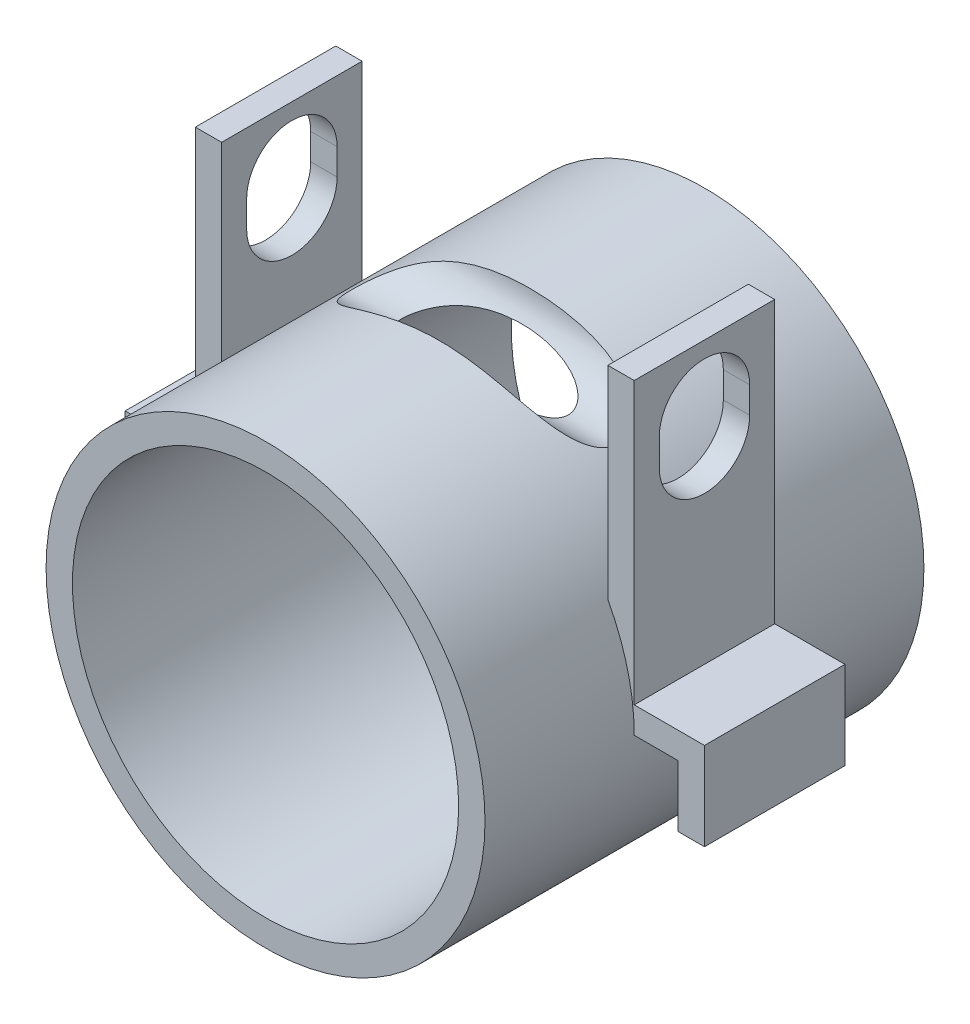
SolidWorks part; units mm, degrees
ref_plane "Front Plane" through (0, 0, 0) normal (0, 0, 1) x (1, 0, 0)
ref_plane "Top Plane" through (0, 0, 0) normal (0, 1, 0) x (1, 0, 0)
ref_plane "Right Plane" through (0, 0, 0) normal (1, 0, 0) x (0, 0, -1)
sketch "Sketch1" plane through (0, 0, 0) normal (0, 0, 1) x (1, 0, 0)
  circle A0 centre (0, 0) radius 22
  circle A1 centre (0, 0) radius 25
  dimension "D1" = 44
  dimension "D2" = 3
extrude "Boss-Extrude1" add sketch "Sketch1" along normal blind 50
ref_plane "Plane1" through (0, 0, 25) normal (0, 0, 1) x (1, 0, 0)
sketch "Sketch3" plane through (0, 0, 0) normal (1, 0, 0) x (0, 0, -1)
  line L0 (0, 25) -> (-50, 25) construction
  circle A0 centre (-25, 25) radius 5.15
  dimension "D1" = 10.3
extrude "Cut-Extrude1" cut sketch "Sketch3" against normal mid plane 50
sketch "Sketch4" plane through (0, 0, 25) normal (0, 0, 1) x (1, 0, 0)
  line L3 (0, 0) -> (50000, 0) construction
  line L4 (-19.776, 25) -> (49980.224, 25) construction
  line L5 (-22, 11.8743) -> (-22, 35)
  line L6 (-25, 0) -> (-25, 35)
  line L7 (-25, 35) -> (-22, 35)
  line L8 (0, 0) -> (0, 11.0861) construction
  circle A3 centre (0, 0) radius 25 construction
  arc A4 (-22, 11.8743) -> (-25, 0) centre (0, 0) ccw
  dimension "D1" = 3
  dimension "D2" = 35
extrude "Boss-Extrude2" add sketch "Sketch4" along normal mid plane 16
sketch "Sketch6" plane through (0, 0, 25) normal (0, 0, 1) x (1, 0, 0)
  line L0 (-25, 35) -> (-25, 0) construction
  line L1 (-25, 0) -> (-33, 0)
  line L2 (-25, 0) -> (-25, 3)
  line L3 (-25, 3) -> (-33, 3)
  line L4 (-33, 0) -> (-33, 3)
  line L5 (-25, 0) -> (-33, 3) construction
  line L6 (-25, 3) -> (-33, 0) construction
  line L7 (-33, 0) -> (-30, 0)
  line L8 (-33, 0) -> (-33, -7)
  line L9 (-33, -7) -> (-30, -7)
  line L10 (-30, 0) -> (-30, -7)
  line L11 (-33, 0) -> (-30, -7) construction
  line L12 (-33, -7) -> (-30, 0) construction
  circle A0 centre (0, 0) radius 25 construction
  arc A1 (-22, 11.8743) -> (-25, 0) centre (0, 0) ccw construction
  point P4 (-29, 1.5)
  point P13 (-31.5, -3.5)
  dimension "D1" = 8
  dimension "D2" = 3
  dimension "D3" = 7
  dimension "D4" = 3
extrude "Boss-Extrude3" add sketch "Sketch6" along normal mid plane 16 contours L4 L1 L2 L3 | L10 L1 L8 L9 region at (-29, 1.5, 25) region at (-31.5, -3.5, 25)
mirror "Mirror1" about plane through (0, 0, 0) normal (1, 0, 0) of "Boss-Extrude3", "Boss-Extrude2"
sketch "Sketch5" plane through (-25, 0, 0) normal (-1, 0, 0) x (0, 0, 1)
  line L0 (25, -27.5) -> (25, 27.5) construction
  line L1 (25, 25) -> (25, 28) construction
  line L6 (19.85, 25) -> (19.85, 28)
  line L7 (30.15, 25) -> (30.15, 28)
  circle A0 centre (25, 25) radius 5.15 construction
  arc A1 (30.15, 25) -> (19.85, 25) centre (25, 25) ccw construction
  arc A2 (19.85, 25) -> (30.15, 25) centre (25, 25) ccw
  arc A3 (30.15, 28) -> (19.85, 28) centre (25, 28) ccw
  point P7 (25, 26.5)
  dimension "D1" = 3
extrude "Cut-Extrude3" cut sketch "Sketch5" against normal through all
